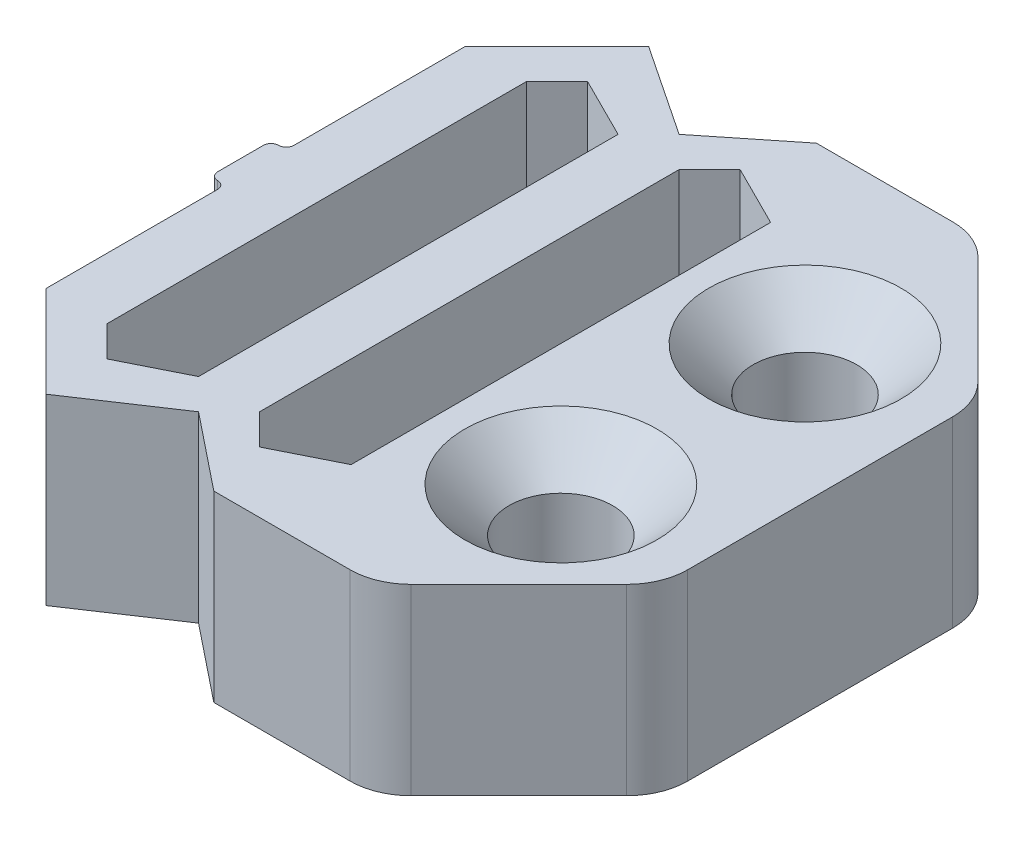
SolidWorks part; units mm, degrees
material "POLYURETHANE (11671)"
ref_plane "Front Plane" through (0, 0, 0) normal (0, 0, 1) x (1, 0, 0)
ref_plane "Top Plane" through (0, 0, 0) normal (0, 1, 0) x (1, 0, 0)
ref_plane "Right Plane" through (0, 0, 0) normal (1, 0, 0) x (0, 0, -1)
sketch "Sketch1" plane through (0, 0, 0) normal (0, 1, 0) x (1, 0, 0)
  line L0 (-8.25, 0) -> (8.25, 0) construction
  line L1 (-55, 0) -> (55, 0) construction
  line L2 (-1.75, -9.875) -> (3.5466, -9.875)
  line L3 (0, -12) -> (0, 12) construction
  line L4 (0, -55) -> (0, 55) construction
  line L5 (8.25, -5.1716) -> (8.25, 5.1716)
  line L6 (-10.25, -9.875) -> (-10.25, -1) construction
  line L11 (-1.75, 9.875) -> (3.5466, 9.875)
  line L12 (3.5466, 9.875) -> (8.25, 5.1716)
  line L17 (3.5466, -9.875) -> (8.25, -5.1716)
  line L24 (-10.25, -1) -> (-10.75, -1)
  line L31 (-10.25, -6.875) -> (-10.25, -1)
  line L34 (-7.25, -9.875) -> (-10.25, -6.875)
  line L36 (-8.25, -6.875) -> (-8.25, 6.875)
  line L37 (-8.25, 6.875) -> (-7.25, 7.875)
  line L38 (-7.25, 7.875) -> (-5.25, 6.875)
  line L39 (-5.25, 6.875) -> (-5.25, -6.875)
  line L40 (-5.25, -6.875) -> (-7.25, -7.875)
  line L41 (-7.25, -7.875) -> (-8.25, -6.875)
  line L42 (-3.25, -6.875) -> (-3.25, 6.875)
  line L43 (-3.25, 6.875) -> (-2.25, 7.875)
  line L44 (-2.25, 7.875) -> (-0.25, 6.875)
  line L45 (-0.25, 6.875) -> (-0.25, -6.875)
  line L46 (-0.25, -6.875) -> (-2.25, -7.875)
  line L47 (-2.25, -7.875) -> (-3.25, -6.875)
  line L48 (-4.25, -7.875) -> (-7.25, -9.875)
  line L49 (-4.25, -7.875) -> (-1.75, -9.875)
  line L50 (-1.75, 9.875) -> (-4.25, 7.875)
  line L51 (-4.25, 7.875) -> (-7.25, 9.875)
  line L52 (-7.25, 9.875) -> (-10.25, 6.875)
  line L53 (-10.75, -1) -> (-10.75, 1)
  line L54 (-10.75, 1) -> (-10.25, 1)
  line L55 (-10.25, 0) -> (-8.25, 0) construction
  line L56 (-10.25, 0) -> (-10.25, 1) construction
  line L57 (-10.25, 1) -> (-10.25, 6.875)
  line L58 (-10.25, 0) -> (-10.25, 1) construction
  line L59 (-10.25, 1) -> (-10.25, 9.875) construction
  line L60 (-10.25, -1) -> (-10.25, 0) construction
  line L61 (-10.25, -1) -> (-10.25, 0) construction
  point P6 (0, 0)
  point P12 (0, 0)
  point P15 (8.25, 0)
  point P18 (-10.25, 0)
  point P24 (-9.25, -1.6962)
  point P26 (0, 0)
  point P28 (0, 0)
  dimension "D1" = 18.5
  dimension "D2" = 24
  dimension "D3" = 19.75
  dimension "D4" = 45
  dimension "D5" = 6.6517
  dimension "D6" = 8.5
  dimension "D7" = 45
  dimension "D13" = 3
  dimension "D14" = 3
  dimension "D15" = 3
  dimension "D16" = 2
  dimension "D17" = 2
  dimension "D18" = 1
  dimension "D19" = 1
  dimension "D20" = 1
  dimension "D21" = 2
  dimension "D22" = 2
  dimension "D23" = 1
  dimension "D8" = 3
  dimension "D9" = 3
  dimension "D10" = 1
  dimension "D11" = 0.5
  dimension "D12" = 1
  dimension "D24" = 19.75
  dimension "D25" = 2
extrude "Boss-Extrude1" add sketch "Sketch1" along normal mid plane 6
fillet "Fillet1" radius 2 4 edges at (3.5466, 0, -9.875) (8.25, 0, -5.1716) (8.25, 0, 5.1716) (3.5466, 0, 9.875)
hole_wizard "CSK for M3 Countersunk Flat Head Screw1" positions "Sketch2" profile "Sketch3" countersink size "M3" standard "DIN" end condition through all
sketch "Sketch2" plane through (0, 3, 0) normal (0, 1, 0) x (1, 0, 0)
  line L0 (8.25, -4.3431) -> (8.25, 4.3431) construction
  line L1 (-55, 0) -> (55, 0) construction
  point P0 (3.75, 4)
  point P2 (3.75, -4)
  dimension "D1" = 8
  dimension "D2" = 4.5
  dimension "D3" = 4
sketch "Sketch3" plane through (3.75, 3, -4) normal (1, 0, 0) x (0, 0, 1)
  line L0 (0, 0) -> (0, 6)
  line L1 (0, 6) -> (1.7, 6)
  line L2 (1.7, 6) -> (1.7, 1.45)
  line L3 (1.7, 1.45) -> (3.15, 0)
  line L5 (3.15, 0) -> (0, 0)
  line L6 (-1.7, 1.45) -> (-3.15, 0) construction
  line L11 (0, -6.35) -> (0, 107.95) construction
  dimension "Thru Hole Dia." = 3.4
  dimension "Thru Hole Depth" = 6
  dimension "Near C'Sink Dia." = 6.3
  dimension "Near C'Sink Angle" = 90
fillet "Fillet2" radius 0.25 4 edges at (-10.25, 0, -1) (-10.75, 0, -1) (-10.75, 0, 1) (-10.25, 0, 1)
equation "\"D3@Sketch2\"=\"D1@Sketch2\"/2"
equation "\"D10@Sketch1\"=\"D12@Sketch1\""
